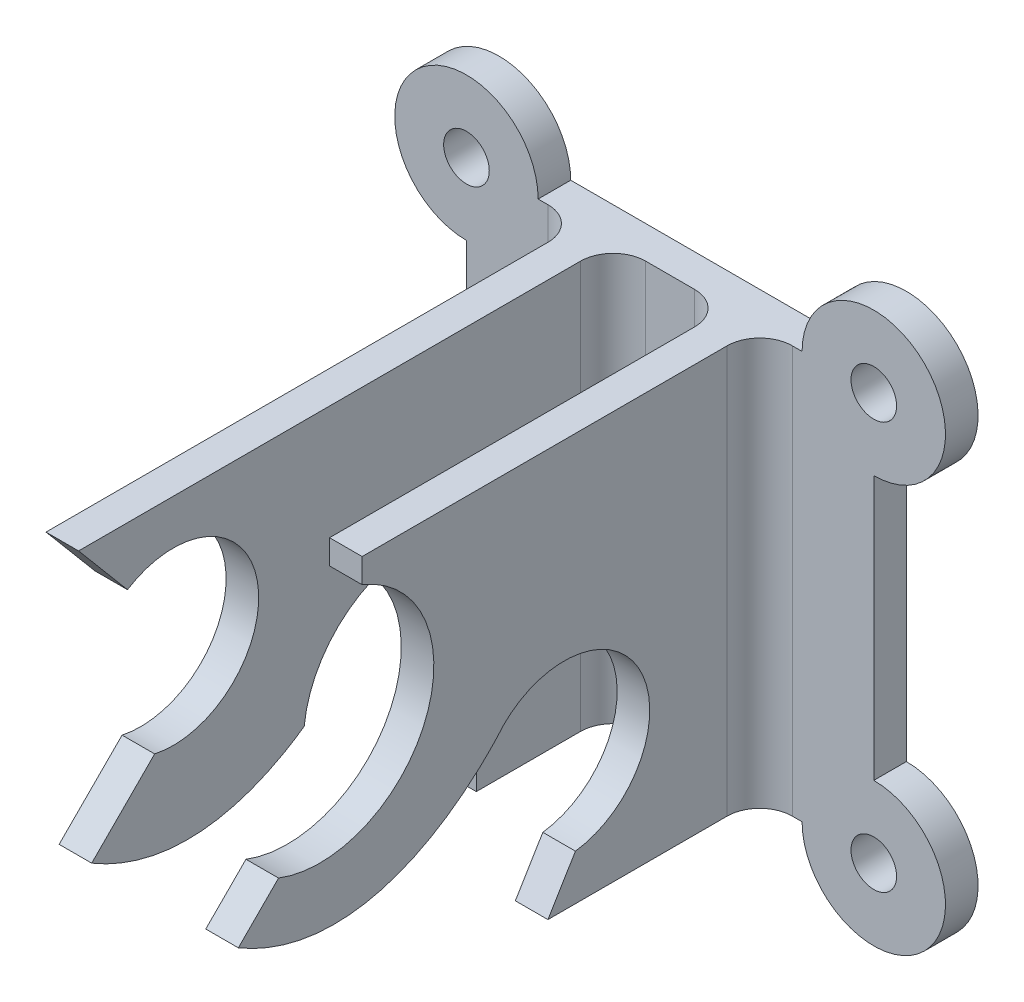
SolidWorks part; units mm, degrees
ref_plane "Front Plane" through (0, 0, 0) normal (0, 0, 1) x (1, 0, 0)
ref_plane "Top Plane" through (0, 0, 0) normal (0, 1, 0) x (1, 0, 0)
ref_plane "Right Plane" through (0, 0, 0) normal (1, 0, 0) x (0, 0, -1)
sketch "Sketch1" plane through (0, 0, 0) normal (0, 0, 1) x (1, 0, 0)
  line L0 (12.5, 25) -> (12.5, 0) construction
  line L1 (0, 0) -> (25, 0)
  line L2 (0, 0) -> (0, 25)
  line L3 (0, 25) -> (25, 25)
  line L4 (25, 0) -> (25, 25)
  line L5 (7, 25) -> (7, 0)
  line L6 (18, 25) -> (18, 0)
  line L7 (9, 25) -> (9, 0)
  line L8 (16, 25) -> (16, 0)
  circle A0 centre (0, 25) radius 1.4
  circle A1 centre (25, 25) radius 1.4
  circle A2 centre (0, 0) radius 1.4
  circle A3 centre (25, 0) radius 1.4
  circle A4 centre (0, 25) radius 4.4
  circle A5 centre (25, 25) radius 4.4
  circle A6 centre (0, 0) radius 4.4
  circle A7 centre (25, 0) radius 4.4
  dimension "D3" = 2.8
  dimension "D4" = 2.8
  dimension "D5" = 2.8
  dimension "D6" = 2.8
  dimension "D1" = 25
  dimension "D2" = 25
  dimension "D8" = 5.5
  dimension "D9" = 5.5
  dimension "D7" = 3
  dimension "D10" = 2
  dimension "D11" = 2
extrude "Boss-Extrude1" add sketch "Sketch1" along normal blind 2 contours L3 A4 L2 A0 | L2 A4 L3 A0 | A6 L1 L5 L3 A4 L2 | L2 A6 L1 A2 | L1 A6 L2 A2 | L0 L3 L7 L1 | L3 L0 L1 L8 | A7 L4 A5 L3 L6 L1 | L3 A5 L4 A1 | L4 A5 L3 A1 | L4 A7 L1 A3 | L1 A7 L4 A3 region at (14.25, 12.5, 0) region at (10.75, 12.5, 0) region at (3.8434, 12.5, 0) region at (21.1566, 12.5, 0) region at (2.0108, 22.9892, 0) region at (2.9, 25.1245, 0) region at (25, 29.2755, 0) region at (22.9892, 22.9892, 0) region at (-3.0233, -3.0233, 0) region at (2.0108, 2.0108, 0) region at (22.9892, 2.0108, 0) region at (22.1, -0.1245, 0)
extrude "Boss-Extrude2" add sketch "Sketch1<3>" along normal blind 40 contours L7 L3 L5 L1 | L3 L8 L1 L6 region at (8, 12.5, 0) region at (17, 12.5, 0)
sketch "Sketch1<3>" plane through (0, 0, 0) normal (0, 0, 1) x (1, 0, 0) same geometry as "Sketch1"
sketch "Sketch2" plane through (7, 0, 0) normal (-1, 0, 0) x (0, 0, 1)
  line L0 (40, 25) -> (2, 25) construction
  line L1 (40, 0) -> (2, 0) construction
  line L2 (2, 25) -> (2, 0) construction
  circle A0 centre (29, 17) radius 5.25
  circle A1 centre (14, 8) radius 7
  dimension "D1" = 10.5
  dimension "D2" = 14
  dimension "D3" = 8
  dimension "D4" = 8
  dimension "D5" = 12
  dimension "D6" = 15
sketch "Sketch3" plane through (18, 0, 0) normal (1, 0, 0) x (0, 0, -1)
  circle A4 centre (-14, 8) radius 5.25
  circle A6 centre (-29, 17) radius 7
  dimension "D1" = 10.5
  dimension "D2" = 14
extrude "Cut-Extrude12" cut sketch "Sketch2" against normal up to next
extrude "Cut-Extrude13" cut sketch "Sketch3" against normal up to next
sketch "Sketch5" plane through (7, 0, 0) normal (-1, 0, 0) x (0, 0, 1)
  line L0 (31.8048, 21.438) -> (34.8048, 25)
  line L1 (40, 25) -> (2, 25) construction
  line L2 (34.8048, 25) -> (40, 25)
  line L3 (40, 25) -> (40, 0)
  line L4 (30.1356, 11.8743) -> (34, 8)
  line L5 (31.8048, 21.438) -> (30.1356, 11.8743)
  line L6 (29.3534, 5.2545) -> (38.6466, 10.7455) construction
  line L7 (13.312, 2.7953) -> (15, 0)
  line L8 (40, 0) -> (2, 0) construction
  line L9 (15, 0) -> (40, 0)
  line L10 (18.1548, 11.2094) -> (13.312, 2.7953)
  line L11 (14.7987, 14.8004) -> (21.5108, 7.6184) construction
  circle A0 centre (29, 17) radius 5.25 construction
  circle A2 centre (14, 8) radius 5.25 construction
  circle A3 centre (14, 8) radius 5.25 construction
  circle A4 centre (29, 17) radius 5.25 construction
  spline S0 degree 3 poles (34, 8) (28.1917, 4.5681) (22.3498, 6.7207) (18.1548, 11.2094) knots 0 0 0 0 1 1 1 1
  dimension "D2" = 2
  dimension "D1" = 2
  dimension "D3" = 3
  dimension "D4" = 6
  dimension "D5" = 8
  dimension "D6" = 25
extrude "Cut-Extrude14" cut sketch "Sketch5" against normal through all
sketch "Sketch6" plane through (7, 0, 0) normal (-1, 0, 0) x (0, 0, 1)
  line L1 (15, 0) -> (10.3944, 0)
  line L2 (15, 0) -> (15, 2)
  line L3 (15, 2) -> (10.3944, 2)
  line L4 (10.3944, 0) -> (10.3944, 2)
  arc A0 (20.9598, 8.7488) -> (14.3896, 1.0108) centre (14, 8) ccw construction
  dimension "D1" = 2
extrude "Cut-Extrude15" cut sketch "Sketch6" against normal up to next
sketch "Sketch7" plane through (18, 0, 0) normal (1, 0, 0) x (0, 0, -1)
  line L1 (-34.8048, 25) -> (-26.4019, 25)
  line L2 (-34.8048, 25) -> (-34.8048, 23.5)
  line L3 (-34.8048, 23.5) -> (-26.4019, 23.5) construction
  line L4 (-26.4019, 25) -> (-26.4019, 23.5)
  arc A0 (-31.5323, 10.4741) -> (-32.94, 22.7859) centre (-29, 17) ccw construction
  arc A1 (-34.8048, 23.5) -> (-26.4019, 23.5) centre (-30.6034, 23.5) ccw
  dimension "D1" = 1.5
extrude "Cut-Extrude16" cut sketch "Sketch7" against normal up to next
fillet "Fillet1" radius 2 4 edges at (18, 12.5, 2) (16, 12.5, 2) (9, 12.5, 2) (7, 12.5, 2)
